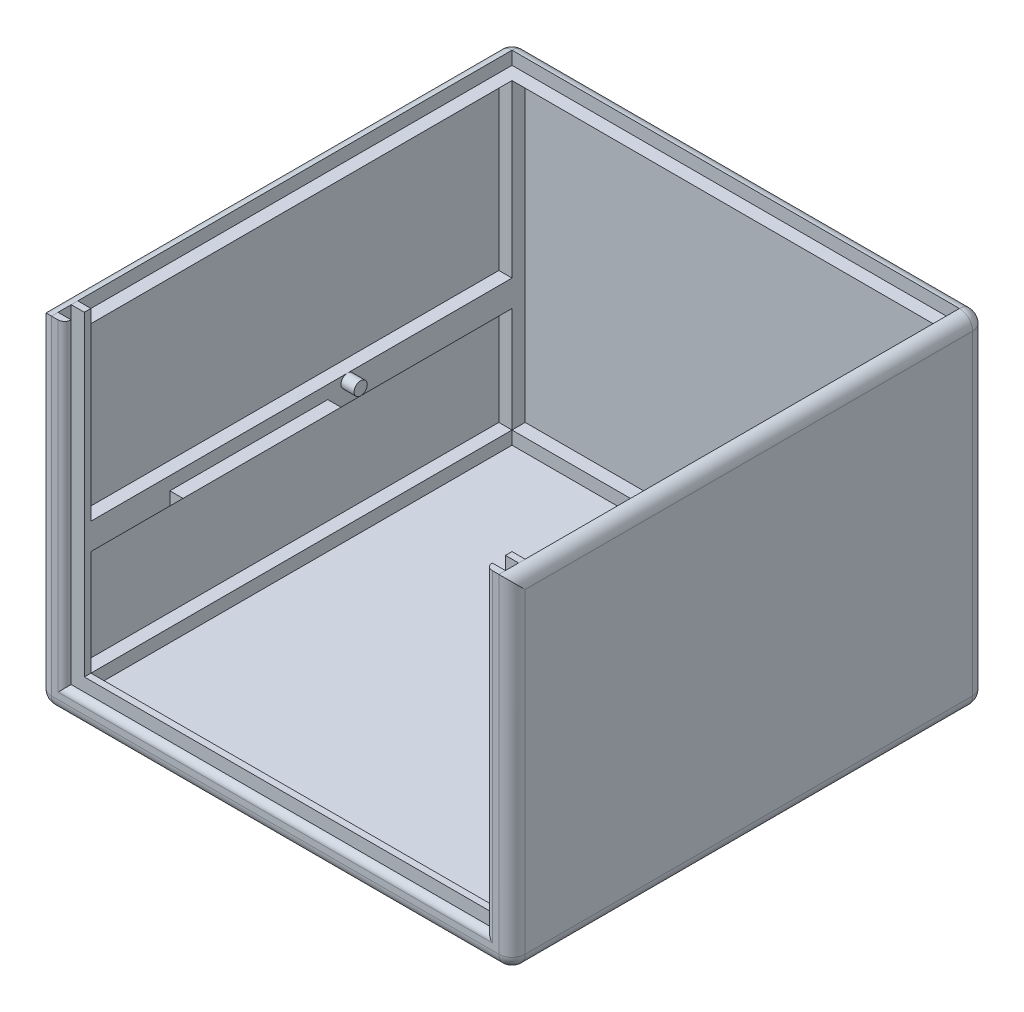
SolidWorks part; units mm, degrees
ref_plane "Ebene vorne" through (0, 0, 0) normal (0, 0, 1) x (1, 0, 0)
ref_plane "Ebene oben" through (0, 0, 0) normal (0, 1, 0) x (1, 0, 0)
ref_plane "Ebene rechts" through (0, 0, 0) normal (1, 0, 0) x (0, 0, -1)
sketch "Sketch5" plane through (0, 0, 0) normal (0, 1, 0) x (1, 0, 0)
  line L1 (90, -90) -> (-90, -90)
  line L2 (90, -90) -> (90, 90)
  line L3 (90, 90) -> (-90, 90)
  line L4 (-90, -90) -> (-90, 90)
  line L5 (90, -90) -> (-90, 90) construction
  line L6 (90, 90) -> (-90, -90) construction
  line L7 (-80, 80) -> (80, 80)
  line L8 (-80, 80) -> (-80, -80)
  line L9 (-80, -80) -> (80, -80)
  line L10 (80, 80) -> (80, -80)
  line L11 (-80, 80) -> (80, -80) construction
  line L12 (-80, -80) -> (80, 80) construction
  point P0 (0, 0)
  point P6 (0, 0)
  dimension "D1" = 10
  dimension "D2" = 10
  dimension "D3" = 180
extrude "Boss-Extrude5" add sketch "Sketch5" along normal blind 10
sketch "Sketch6" plane through (0, 10, 0) normal (0, 1, 0) x (1, 0, 0)
  line L1 (90, -90) -> (80, -90)
  line L2 (90, -90) -> (90, -80)
  line L3 (90, -80) -> (80, -80)
  line L4 (80, -90) -> (80, -80)
  line L5 (90, 90) -> (80, 90)
  line L6 (90, 90) -> (90, 80)
  line L7 (90, 80) -> (80, 80)
  line L8 (80, 90) -> (80, 80)
  line L9 (-90, 90) -> (-80, 90)
  line L10 (-90, 90) -> (-90, 80)
  line L11 (-90, 80) -> (-80, 80)
  line L12 (-80, 90) -> (-80, 80)
  line L13 (-90, -90) -> (-80, -90)
  line L14 (-90, -90) -> (-90, -80)
  line L15 (-90, -80) -> (-80, -80)
  line L16 (-80, -90) -> (-80, -80)
extrude "Boss-Extrude6" add sketch "Sketch6" along normal blind 120
sketch "Sketch7" plane through (0, 0, 90) normal (0, 0, 1) x (1, 0, 0)
  line L0 (80, 130) -> (80, 10) construction
  line L1 (80, 60) -> (90, 60)
  line L2 (80, 60) -> (80, 50)
  line L3 (80, 50) -> (90, 50)
  line L4 (90, 60) -> (90, 50)
  line L5 (90, 130) -> (90, 0) construction
  line L6 (-90, 130) -> (-90, 0) construction
  line L7 (-90, 60) -> (-80, 60)
  line L8 (-90, 60) -> (-90, 50)
  line L9 (-90, 50) -> (-80, 50)
  line L10 (-80, 60) -> (-80, 50)
  line L11 (-80, 130) -> (-80, 10) construction
  line L12 (-80, 10) -> (80, 10) construction
  dimension "D1" = 40
  dimension "D2" = 40
extrude "Boss-Extrude7" add sketch "Sketch7" against normal blind 177.7703
sketch "Sketch9" plane through (0, 0, 0) normal (0, -1, 0) x (-1, 0, 0)
  line L1 (80, -80) -> (-80, -80)
  line L2 (80, -80) -> (80, 80)
  line L3 (80, 80) -> (-80, 80)
  line L4 (-80, -80) -> (-80, 80)
sketch "Sketch10" plane through (-80, 0, 0) normal (1, 0, 0) x (0, 0, -1)
  line L0 (-50, 55) -> (10, 55)
  line L2 (10, 55) -> (10, 50)
  line L3 (10, 50) -> (-50, 50)
  line L4 (-50, 50) -> (-50, 55)
  line L5 (-80, 60) -> (-80, 50) construction
  line L6 (80, 50) -> (-80, 50) construction
  line L8 (80, 60) -> (-80, 60) construction
  circle A0 centre (17.5, 57.5) radius 2.5
  dimension "D4" = 5
  dimension "D1" = 30
  dimension "D2" = 5
  dimension "D3" = 60
  dimension "D5" = 2.5
  dimension "D6" = 7.5
extrude "Boss-Extrude9" add sketch "Sketch10" along normal blind 5
sketch "Sketch11" plane through (0, 0, 50) normal (0, 0, 1) x (1, 0, 0)
  line L0 (-75, 55) -> (-80, 50)
  line L1 (-80, 50) -> (-75, 50)
  line L2 (-75, 50) -> (-75, 55)
extrude "Cut-Extrude1" cut sketch "Sketch11" against normal through all both and the other way through all
mirror "Mirror1" about plane through (0, 0, 0) normal (1, 0, 0) of "Cut-Extrude1", "Boss-Extrude9"
sketch "Sketch12" plane through (0, 0, 0) normal (0, -1, 0) x (1, 0, 0)
  line L1 (-80, 80) -> (80, 80)
  line L2 (-80, 80) -> (-80, -80)
  line L3 (-80, -80) -> (80, -80)
  line L4 (80, 80) -> (80, -80)
extrude "Boss-Extrude10" add sketch "Sketch12" against normal blind 5
sketch "Sketch14" plane through (0, 0, -90) normal (0, 0, -1) x (-1, 0, 0)
  line L1 (-80, 130) -> (80, 130)
  line L2 (-80, 130) -> (-80, 10)
  line L3 (-80, 10) -> (80, 10)
  line L4 (80, 130) -> (80, 10)
extrude "Boss-Extrude12" add sketch "Sketch14" against normal blind 5
sketch "Sketch15" plane through (0, 0, 90) normal (0, 0, 1) x (1, 0, 0)
  line L0 (-90, 125) -> (-80, 125)
  line L1 (-80, 125) -> (-90, 115)
  line L2 (-90, 130) -> (-90, 0) construction
  line L3 (-90, 115) -> (-90, 125)
  line L4 (-80, 10) -> (-80, 130) construction
  line L5 (-90, 130) -> (-80, 130) construction
  line L6 (0, -5.5) -> (0, 5.5) construction
  line L7 (90, 115) -> (90, 125)
  line L8 (80, 125) -> (90, 115)
  line L9 (90, 125) -> (80, 125)
  dimension "D1" = 45
  dimension "D2" = 5
extrude "Boss-Extrude13" add sketch "Sketch15" against normal blind 170.9779
sketch "Sketch16" plane through (90, 0, 0) normal (1, 0, 0) x (0, 0, -1)
  line L1 (-80, 130) -> (80, 130)
  line L2 (-80, 130) -> (-80, 10)
  line L3 (-80, 10) -> (80, 10)
  line L4 (80, 130) -> (80, 10)
extrude "Boss-Extrude14" add sketch "Sketch16" against normal blind 5
sketch "Sketch17" plane through (-90, 0, 0) normal (-1, 0, 0) x (0, 0, 1)
  line L1 (-80, 130) -> (80, 130)
  line L2 (-80, 130) -> (-80, 10)
  line L3 (-80, 10) -> (80, 10)
  line L4 (80, 130) -> (80, 10)
extrude "Boss-Extrude15" add sketch "Sketch17" against normal blind 5
sketch "Sketch18" plane through (0, 130, 0) normal (0, 1, 0) x (1, 0, 0)
  line L1 (-80, -85) -> (-90, -85) construction
  line L2 (-80, -90) -> (-80, -80) construction
  line L3 (-90, 90) -> (-90, -90) construction
  line L4 (-85, -90) -> (-85, -80) construction
  line L5 (-90, -90) -> (-80, -90) construction
  line L7 (85, -87.5) -> (-85, -87.5)
  line L8 (85, -87.5) -> (85, -82.5)
  line L9 (85, -82.5) -> (-85, -82.5)
  line L10 (-85, -87.5) -> (-85, -82.5)
  dimension "D2" = 170
  dimension "D3" = 2.5
extrude "Cut-Extrude2" cut sketch "Sketch18" against normal blind 125 and the other way through all
sketch "Sketch19" plane through (-80, 0, 0) normal (1, 0, 0) x (0, 0, -1)
  line L0 (80, 125) -> (85, 125)
  line L1 (85, 10) -> (85, 130) construction
  line L2 (85, 125) -> (85, 120)
  line L3 (85, 120) -> (80, 125)
  dimension "D1" = 45
extrude "Boss-Extrude16" add sketch "Sketch19" along normal up to next
sketch "Sketch20" plane through (0, 130, 0) normal (0, 1, 0) x (1, 0, 0)
  line L0 (-80, 85) -> (-90, 85) construction
  line L1 (-90, 90) -> (-90, -90) construction
  line L2 (0, -71.5) -> (0, 71.5) construction
  line L3 (-85, 85) -> (-80, 85)
  line L4 (-85, 85) -> (-85, 80)
  line L5 (-85, 80) -> (-80, 80)
  line L6 (-80, 85) -> (-80, 80)
  line L7 (85, 80) -> (80, 80)
  line L8 (80, 85) -> (80, 80)
  line L9 (85, 85) -> (80, 85)
  line L10 (85, 85) -> (85, 80)
extrude "Cut-Extrude4" cut sketch "Sketch20" against normal blind 5
fillet "Fillet4" radius 5 11 edges at (0, 130, -90) (-90, 65, -90) (-90, 130, 0) (90, 130, 0) (90, 65, -90) (90, 65, 90) (-90, 65, 90) (0, 0, 90) (90, 0, 0) (0, 0, -90) (-90, 0, 0)
fillet "Fillet6" radius 2.5 3 edges at (-80, 70, 90) (80, 70, 90) (0, 10, 90)
extrude "Boss-Extrude8" add sketch "Sketch9" against normal blind 5
